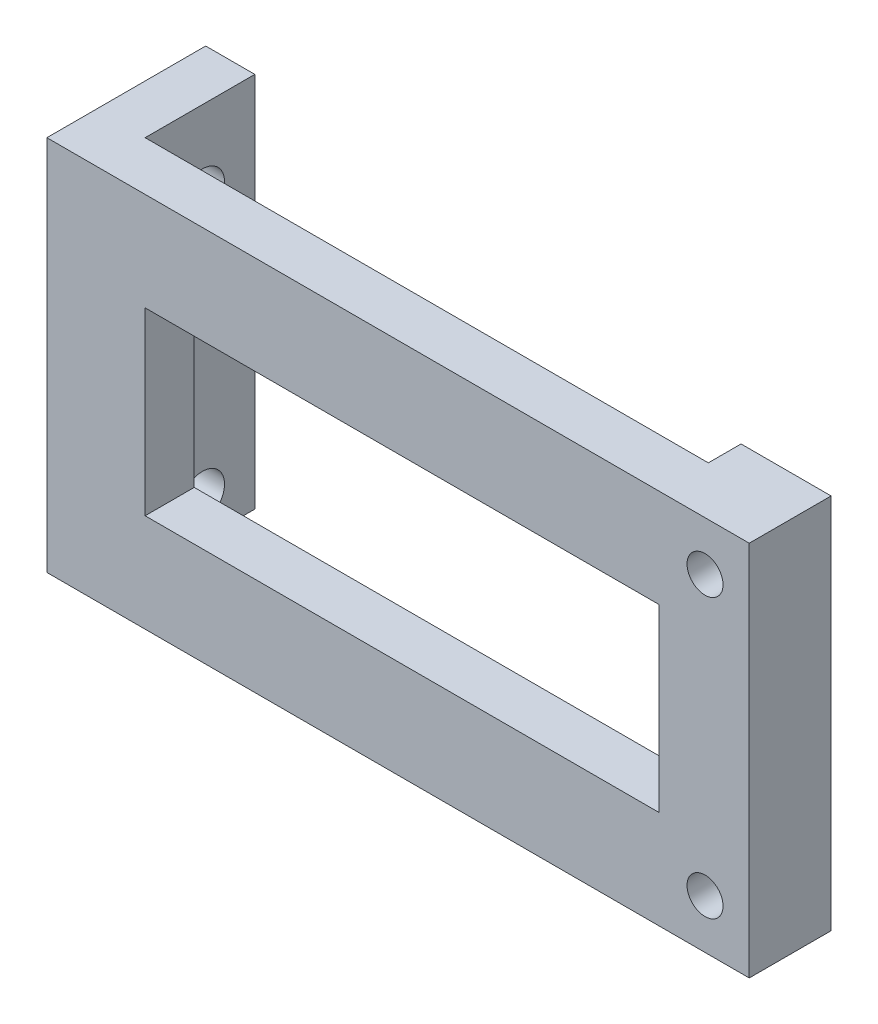
SolidWorks part; units mm, degrees
ref_plane "Front Plane" through (0, 0, 0) normal (0, 0, 1) x (1, 0, 0)
ref_plane "Top Plane" through (0, 0, 0) normal (0, 1, 0) x (1, 0, 0)
ref_plane "Right Plane" through (0, 0, 0) normal (1, 0, 0) x (0, 0, -1)
sketch "Sketch1" plane through (0, 0, 0) normal (0, 0, 1) x (1, 0, 0)
  line L0 (-15.45, 11.5) -> (-15.45, 5.5) construction
  line L1 (21.45, 11.5) -> (-21.45, 11.5)
  line L2 (21.45, 11.5) -> (21.45, -11.5)
  line L3 (21.45, -11.5) -> (-21.45, -11.5)
  line L4 (-21.45, 11.5) -> (-21.45, -11.5)
  line L5 (21.45, 11.5) -> (-21.45, -11.5) construction
  line L6 (21.45, -11.5) -> (-21.45, 11.5) construction
  line L7 (-21.45, 11.5) -> (-18.45, 11.5)
  line L8 (-21.45, 11.5) -> (-21.45, -11.5)
  line L9 (-21.45, -11.5) -> (-18.45, -11.5)
  line L10 (-18.45, 11.5) -> (-18.45, -11.5)
  line L11 (21.45, 11.5) -> (15.95, 11.5)
  line L12 (21.45, 11.5) -> (21.45, -11.5)
  line L13 (21.45, -11.5) -> (15.95, -11.5)
  line L14 (15.95, 11.5) -> (15.95, -11.5)
  line L15 (-15.45, 5.5) -> (15.95, 5.5)
  line L16 (-15.45, 5.5) -> (-15.45, -5.5)
  line L17 (-15.45, -5.5) -> (15.95, -5.5)
  line L18 (15.95, 5.5) -> (15.95, -5.5)
  line L19 (-15.45, 5.5) -> (-21.45, 5.5) construction
  line L20 (-15.45, -5.5) -> (-15.45, -11.5) construction
  circle A0 centre (18.75, -8.5) radius 1.1
  circle A1 centre (18.75, 8.5) radius 1.1
  point P0 (0, 0)
  dimension "D1" = 2.2
  dimension "D2" = 3
  dimension "D3" = 17
  dimension "D4" = 3
  dimension "D5" = 5.5
  dimension "D6" = 2.8
  dimension "D7" = 40.2
  dimension "D8" = 3
  dimension "D9" = 6
extrude "Boss-Extrude1" add sketch "Sketch1" against normal blind 3 contours L14 L1 L10 L3 region at (15.5362, 8.5, 0)
extrude "Boss-Extrude2" add sketch "Sketch1<3>" against normal blind 5 contours L1 L14 L3 L2 A1 A0 region at (18.6968, 0, 0)
sketch "Sketch1<3>" plane through (0, 0, 0) normal (0, 0, 1) x (1, 0, 0) same geometry as "Sketch1"
extrude "Boss-Extrude3" add sketch "Sketch1<4>" against normal blind 9.7 contours L10 L1 L4 L3 region at (-19.95, 0, 0)
sketch "Sketch1<4>" plane through (0, 0, 0) normal (0, 0, 1) x (1, 0, 0) same geometry as "Sketch1"
sketch "Sketch2" plane through (-21.45, 0, 0) normal (-1, 0, 0) x (0, 0, 1)
  line L1 (0, 11.5) -> (0, -11.5) construction
  circle A0 centre (-6.5, 6.75) radius 1.35
  dimension "D1" = 2.7
  dimension "D2" = 1.75
  dimension "D3" = 6.5
extrude "Cut-Extrude1" cut sketch "Sketch2" against normal up to surface (3 mm away) up to face at (-18.45, 0, -6.35)
pattern_linear "LPattern1" count 2 spacing 16 along (0, -1, 0) of "Cut-Extrude1"
move or copy body "Body-Move/Copy1" [suppressed] bodies to move or copy 105
